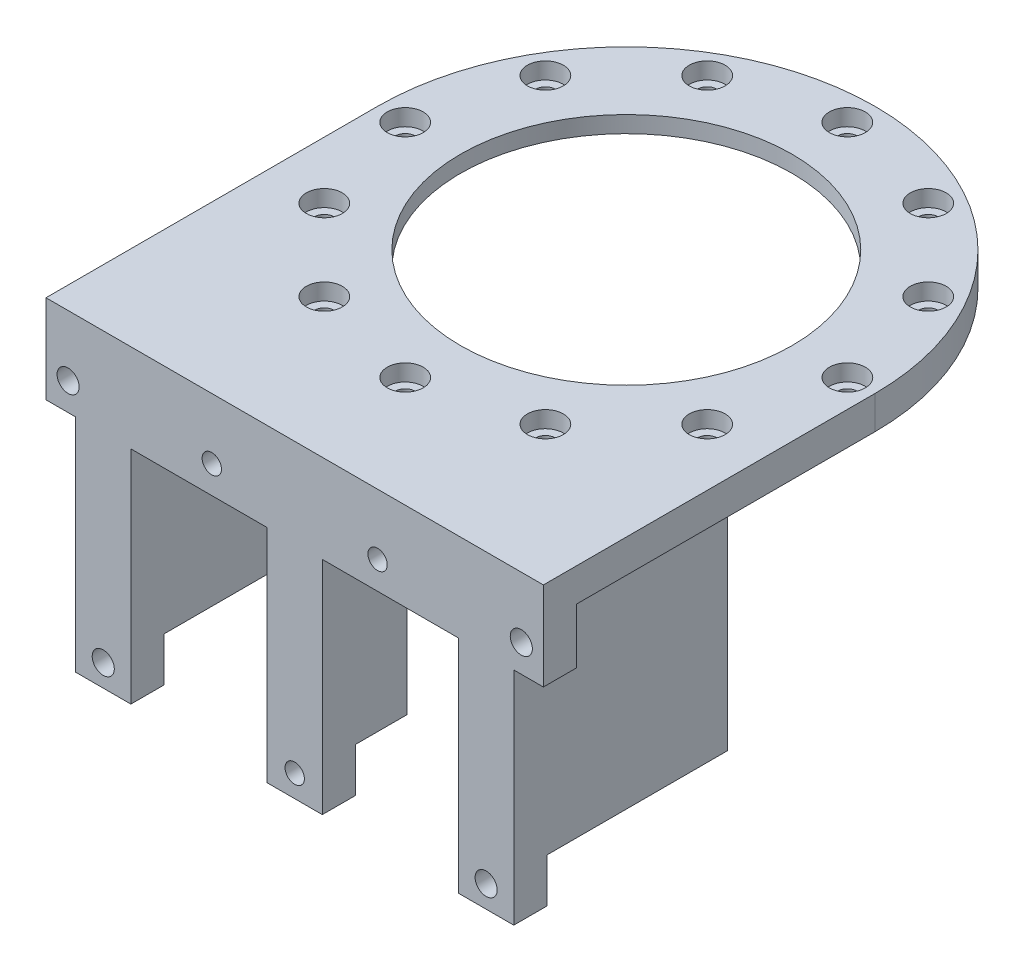
SolidWorks part; units mm, degrees
ref_plane "Front Plane" through (0, 0, 0) normal (0, 0, 1) x (1, 0, 0)
ref_plane "Top Plane" through (0, 0, 0) normal (0, 1, 0) x (1, 0, 0)
ref_plane "Right Plane" through (0, 0, 0) normal (1, 0, 0) x (0, 0, -1)
sketch "Sketch1" plane through (0, 0, 0) normal (0, 1, 0) x (1, 0, 0)
  line L0 (0, 0) -> (0, 52.0165) construction
  circle A0 centre (0, 0) radius 45
  circle A1 centre (0, 0) radius 30
  circle A2 centre (0, 0) radius 40 construction
  circle A3 centre (0, 40) radius 1.75
  circle A4 centre (0, 0) radius 36 construction
  circle A5 centre (20, 34.641) radius 1.75
  circle A6 centre (34.641, 20) radius 1.75
  circle A7 centre (40, 0) radius 1.75
  circle A8 centre (34.641, -20) radius 1.75
  circle A9 centre (20, -34.641) radius 1.75
  circle A10 centre (0, -40) radius 1.75
  circle A11 centre (-20, -34.641) radius 1.75
  circle A12 centre (-34.641, -20) radius 1.75
  circle A13 centre (-40, 0) radius 1.75
  circle A14 centre (-34.641, 20) radius 1.75
  circle A15 centre (-20, 34.641) radius 1.75
  point P21 (0, 0)
  point P34 (0, 0)
  point P48 (0, 0)
  point P72 (0, 0)
  dimension "D1" = 90
  dimension "D2" = 60
  dimension "D4" = 3.5
  dimension "D5" = 72
  dimension "D6" = 12
  dimension "D3" = 80
extrude "Boss-Extrude1" add sketch "Sketch1" along normal blind 6
sketch "Sketch2" plane through (0, 0, 0) normal (0, -1, 0) x (1, 0, 0)
  circle A0 centre (0, 0) radius 36
  dimension "D1" = 72
extrude "Cut-Extrude1" cut sketch "Sketch2" against normal blind 3
sketch "Sketch3" plane through (0, 6, 0) normal (0, 1, 0) x (1, 0, 0)
  line L0 (0, 0) -> (49.8808, 0) construction
  circle A0 centre (40, 0) radius 3.25
  circle A1 centre (34.641, -20) radius 3.25
  circle A2 centre (20, -34.641) radius 3.25
  circle A3 centre (0, -40) radius 3.25
  circle A4 centre (-20, -34.641) radius 3.25
  circle A5 centre (-34.641, -20) radius 3.25
  circle A6 centre (-40, 0) radius 3.25
  circle A7 centre (-34.641, 20) radius 3.25
  circle A8 centre (-20, 34.641) radius 3.25
  circle A9 centre (0, 40) radius 3.25
  circle A10 centre (20, 34.641) radius 3.25
  circle A11 centre (34.641, 20) radius 3.25
  point P30 (0, 0)
  dimension "D1" = 6.5
  dimension "D2" = 12
extrude "Cut-Extrude2" cut sketch "Sketch3" against normal blind 3
sketch "Sketch4" plane through (0, 0, 0) normal (0, -1, 0) x (1, 0, 0)
  line L0 (45, 0) -> (45, 60)
  line L1 (-45, 0) -> (-45, 60)
  line L2 (45, 60) -> (-45, 60)
  line L3 (45, 0) -> (-45, 0) construction
  circle A1 centre (0, 0) radius 45 construction
  arc A2 (45, 0) -> (-45, 0) centre (0, 0) ccw
  dimension "D1" = 60
  dimension "D2" = 90
extrude "Boss-Extrude4" add sketch "Sketch4" against normal blind 6
sketch "Sketch5" plane through (0, 0, 0) normal (0, -1, 0) x (1, 0, 0)
  line L0 (45, 0) -> (45, 60) construction
  line L1 (45, 54) -> (-45, 54)
  line L2 (45, 54) -> (45, 60)
  line L3 (45, 60) -> (-45, 60)
  line L4 (-45, 54) -> (-45, 60)
  dimension "D1" = 6
extrude "Boss-Extrude6" add sketch "Sketch5" along normal blind 10
sketch "Sketch6" plane through (0, 0, 0) normal (0, -1, 0) x (1, 0, 0)
  line L0 (0, 0) -> (0, 68.4249) construction
  line L1 (34.641, 20) -> (34.641, 68.4249) construction
  line L2 (39.641, 21.2976) -> (39.641, 60)
  line L3 (45, 60) -> (-45, 60) construction
  line L4 (39.641, 60) -> (29.641, 60)
  line L5 (29.641, 60) -> (29.641, 33.8587)
  line L6 (-5, 60) -> (5, 60)
  line L7 (5, 60) -> (5, 44.7214)
  line L8 (-5, 60) -> (-5, 44.7214)
  line L9 (-29.641, 60) -> (-29.641, 33.8587)
  line L10 (-39.641, 60) -> (-29.641, 60)
  line L11 (-39.641, 21.2976) -> (-39.641, 60)
  arc A0 (39.641, 21.2976) -> (29.641, 33.8587) centre (0, 0) ccw
  arc A1 (5, 44.7214) -> (-5, 44.7214) centre (0, 0) ccw
  arc A2 (-39.641, 21.2976) -> (-29.641, 33.8587) centre (0, 0) cw
  point P17 (0, 60)
  dimension "D1" = 90
  dimension "D2" = 5
  dimension "D3" = 5
  dimension "D4" = 5
extrude "Boss-Extrude7" add sketch "Sketch6" along normal blind 50
sketch "Sketch7" plane through (39.641, 0, 0) normal (1, 0, 0) x (0, 0, -1)
  line L0 (-21.2976, -42) -> (-54, -42)
  line L1 (-21.2976, -50) -> (-21.2976, 0) construction
  line L2 (-54, -42) -> (-54, -50)
  line L3 (-21.2976, -50) -> (-60, -50) construction
  line L4 (-60, -50) -> (-60, -10) construction
  line L5 (-21.2976, -42) -> (-21.2976, -50)
  line L6 (-21.2976, -50) -> (-54, -50)
  dimension "D1" = 6
  dimension "D2" = 8
extrude "Cut-Extrude3" cut sketch "Sketch7" against normal through all
sketch "Sketch8" plane through (0, 0, 54) normal (0, 0, -1) x (-1, 0, 0)
  line L0 (45, -5) -> (-45, -5) construction
  line L1 (45, -10) -> (45, 0) construction
  line L2 (-45, -10) -> (-45, 0) construction
  line L3 (34.641, -50) -> (34.641, -42) construction
  line L4 (39.641, -50) -> (29.641, -50) construction
  line L5 (39.641, -42) -> (29.641, -42) construction
  line L6 (0, -50) -> (0, -42) construction
  line L7 (5, -50) -> (-5, -50) construction
  line L8 (5, -42) -> (-5, -42) construction
  line L9 (-34.641, -50) -> (-34.641, -42) construction
  line L10 (-29.641, -50) -> (-39.641, -50) construction
  line L11 (-39.641, -42) -> (-29.641, -42) construction
  circle A0 centre (41, -5) radius 2
  circle A1 centre (34.641, -46) radius 2
  circle A2 centre (0, -46) radius 1.75
  circle A3 centre (15, -5) radius 1.75
  circle A4 centre (-34.641, -46) radius 2
  circle A5 centre (-41, -5) radius 2
  circle A6 centre (-15, -5) radius 1.75
  point P32 (0, -5)
  dimension "D1" = 4
  dimension "D3" = 4
  dimension "D5" = 3.5
  dimension "D7" = 3.5
  dimension "D2" = 4
  dimension "D4" = 4
  dimension "D6" = 4
  dimension "D8" = 15
extrude "Cut-Extrude5" cut sketch "Sketch8" against normal through all
